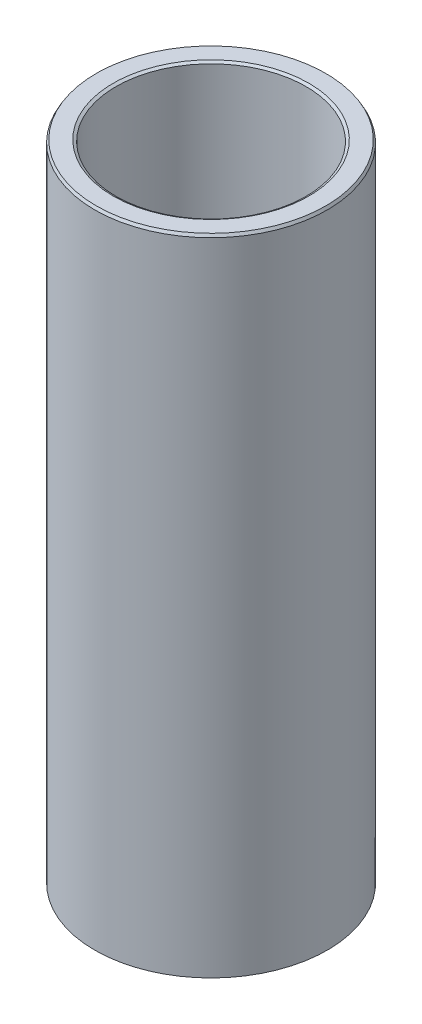
SolidWorks part; units mm, degrees
ref_plane "Front Plane" through (0, 0, 0) normal (0, 0, 1) x (1, 0, 0)
ref_plane "Top Plane" through (0, 0, 0) normal (0, 1, 0) x (1, 0, 0)
ref_plane "Right Plane" through (0, 0, 0) normal (1, 0, 0) x (0, 0, -1)
sketch "Sketch1" plane through (0, 0, 0) normal (0, 1, 0) x (1, 0, 0)
  circle A0 centre (0, 0) radius 52.5
  dimension "SLEEVE_OD" = 105
extrude "Boss-Extrude1" add sketch "Sketch1" along normal blind 291.2733
sketch "Sketch2" plane through (0, 0, 0) normal (0, 1, 0) x (1, 0, 0)
  circle A0 centre (0, 0) radius 42.9184
  dimension "BORE_D" = 85.8368
extrude "Cut-Extrude1" cut sketch "Sketch2" along normal through all
chamfer "Chamfer1" distance 1.2217 angle 30 4 edges at (0, 291.2733, 42.9184) (0, 0, 42.9184) (0, 0, 52.5) (0, 291.2733, 52.5) first distance on face at (0, 291.2733, 42.9184) first distance on face at (0, 0, 42.9184) first distance on face at (0, 291.2733, 52.5)
